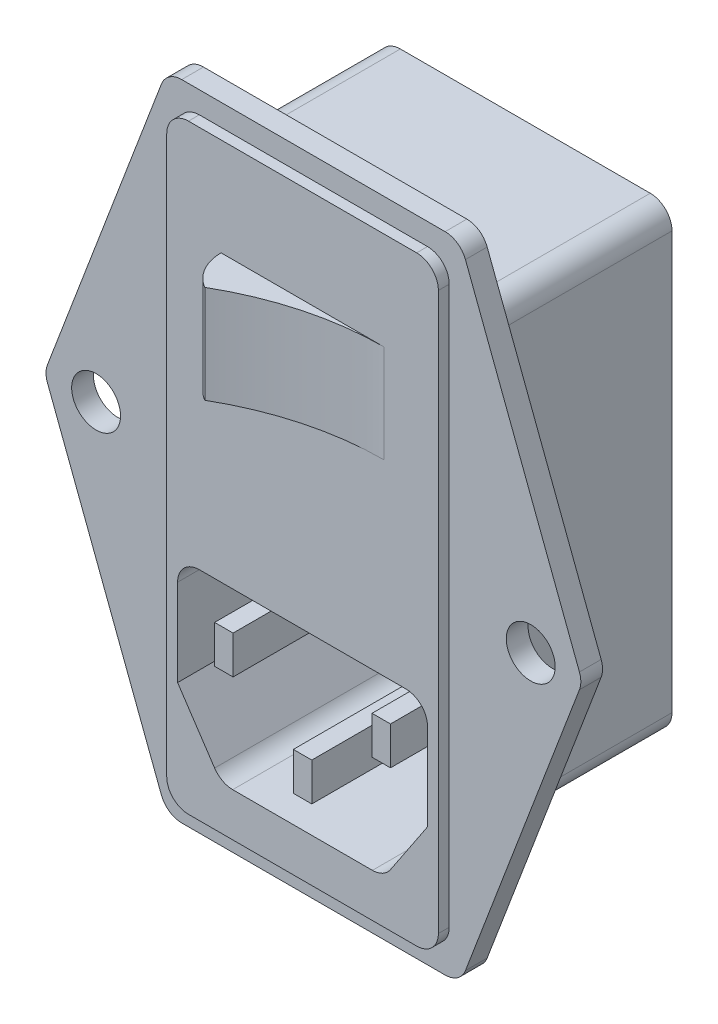
SolidWorks part; units mm, degrees
ref_plane "Спереди" through (0, 0, 0) normal (0, 0, 1) x (1, 0, 0)
ref_plane "Сверху" through (0, 0, 0) normal (0, 1, 0) x (1, 0, 0)
ref_plane "Справа" through (0, 0, 0) normal (1, 0, 0) x (0, 0, -1)
sketch "Эскиз1" plane through (0, 0, 0) normal (0, 0, 1) x (1, 0, 0)
  line L0 (0, 0) -> (27, 0)
  line L1 (0, 0) -> (0, -41.25)
  line L2 (27, 0) -> (27, -41.25)
  line L3 (0, -41.25) -> (27, -41.25) construction
  line L4 (13.5, 0) -> (13.5, -41.25) construction
  line L5 (13.5, -41.25) -> (13.5, -47.25) construction
  line L6 (6.25, -47.25) -> (20.75, -47.25)
  line L7 (0, -41.25) -> (6.25, -47.25)
  line L8 (20.75, -47.25) -> (27, -41.25)
  dimension "D1" = 27
  dimension "D2" = 41.25
  dimension "D3" = 47.25
  dimension "D4" = 14.5
extrude "Бобышка-Вытянуть1" add sketch "Эскиз1" along normal blind 17.5
sketch "Эскиз2" plane through (0, 0, 17.5) normal (0, 0, 1) x (1, 0, 0)
  line L0 (13.5, 0) -> (13.5, -47.25) construction
  line L1 (27, 0) -> (0, 0) construction
  line L2 (6.25, -47.25) -> (20.75, -47.25) construction
  line L3 (13.5, 0) -> (13.5, 7) construction
  line L4 (13.5, -47.25) -> (13.5, -52.25) construction
  line L5 (0, 7) -> (27, 7)
  line L6 (0, -52.25) -> (27, -52.25)
  line L7 (27, 7) -> (27, -52.25) construction
  line L8 (27, -22.625) -> (13.5, -22.625) construction
  line L9 (38.25, -22.625) -> (-11.25, -22.625) construction
  line L10 (0, 7) -> (-11.25, -22.625)
  line L11 (-11.25, -22.625) -> (0, -52.25)
  line L12 (27, 7) -> (38.25, -22.625)
  line L13 (38.25, -22.625) -> (27, -52.25)
  dimension "D1" = 5
  dimension "D2" = 7
  dimension "D3" = 27
  dimension "D4" = 49.5
extrude "Бобышка-Вытянуть2" add sketch "Эскиз2" along normal blind 2
sketch "Эскиз3" plane through (0, 0, 19.5) normal (0, 0, 1) x (1, 0, 0)
  line L0 (13.5, 7) -> (13.5, -52.25) construction
  line L1 (27, 7) -> (0, 7) construction
  line L2 (0, -52.25) -> (27, -52.25) construction
  line L3 (1, 5) -> (26, 5)
  line L4 (1, 5) -> (1, -50.25)
  line L5 (26, 5) -> (26, -50.25)
  line L6 (1, -50.25) -> (26, -50.25)
  line L7 (26, -22.625) -> (1, -22.625) construction
  point P10 (13.5, -22.625)
  dimension "D1" = 2
  dimension "D2" = 25
extrude "Бобышка-Вытянуть3" add sketch "Эскиз3" along normal blind 1
fillet "Скругление1" radius 2 4 edges at (0, 7, 18.5) (27, -52.25, 18.5) (38.25, -22.625, 18.5) (27, 7, 18.5)
fillet "Скругление2" radius 2 2 edges at (0, -52.25, 18.5) (-11.25, -22.625, 18.5)
fillet "Скругление3" radius 2 4 edges at (26, 5, 20) (26, -50.25, 20) (1, -50.25, 20) (1, 5, 20)
sketch "Эскиз4" plane through (0, 0, 20.5) normal (0, 0, 1) x (1, 0, 0)
  line L0 (13.5, 5) -> (13.5, -50.25) construction
  line L1 (24, 5) -> (3, 5) construction
  line L2 (3, -50.25) -> (24, -50.25) construction
  line L3 (6, -4) -> (21, -4)
  line L4 (6, -4) -> (6, -13)
  line L5 (21, -4) -> (21, -13)
  line L6 (6, -13) -> (21, -13)
  line L7 (13.5, -4) -> (13.5, -13) construction
  dimension "D1" = 9
  dimension "D2" = 15
  dimension "D3" = 9
extrude "Бобышка-Вытянуть4" add sketch "Эскиз4" along normal blind 3.5
sketch "Эскиз5" plane through (0, -4, 0) normal (0, 1, 0) x (1, 0, 0)
  line L0 (21, -24) -> (6, -24) construction
  line L1 (6, -24) -> (6, -20.5) construction
  line L2 (6, -24) -> (6, -20.5)
  line L3 (21, -24) -> (6, -24)
  line L4 (21, -20.5) -> (6, -20.5) construction
  line L5 (21, -24) -> (21, -20.5) construction
  line L6 (21, -24) -> (21, -20.5)
  arc A0 (21, -20.5) -> (8, -24) centre (21, -46.3929) ccw
  arc A1 (6, -20.5) -> (8, -24) centre (10.0625, -20.5) ccw
  point P2 (8, -24)
  line M3 (6, -20.5) -> (6, -24)
  line M4 (6, -24) -> (21, -24)
  line M5 (21, -24) -> (21, -20.5)
  dimension "D1" = 2
extrude "Вырез-Вытянуть1" cut sketch "Эскиз5" against normal up to surface (9 mm away) contours A0 L3 M5 | A1 M3 M4 region at (16.0778, -4, 22.5916) region at (6.5621, -4, 23.1738) up to face at (13.5, -13, 22.25)
sketch "Эскиз6" plane through (0, 0, 20.5) normal (0, 0, 1) x (1, 0, 0)
  line L0 (4, -30.25) -> (23, -30.25)
  line L1 (2, -30.25) -> (2, -46.25) construction
  line L2 (25, -30.25) -> (25, -46.25) construction
  line L3 (2, -46.25) -> (25, -46.25) construction
  line L4 (3, -50.25) -> (24, -50.25) construction
  line L5 (13.5, 5) -> (13.5, -50.25) construction
  line L6 (24, 5) -> (3, 5) construction
  line L7 (2, -40.25) -> (5.4063, -45.3594)
  line L8 (7.0704, -46.25) -> (19.9296, -46.25)
  line L9 (2, -32.25) -> (2, -40.25)
  line L10 (2, -40.25) -> (25, -40.25) construction
  line L11 (21.5937, -45.3594) -> (25, -40.25)
  line L12 (25, -40.25) -> (25, -32.25)
  line L13 (5.4063, -33.75) -> (5.4063, -37.25)
  line L14 (5.4063, -33.75) -> (7.1063, -33.75)
  line L15 (5.4063, -37.25) -> (7.1063, -37.25)
  line L16 (7.1063, -33.75) -> (7.1063, -37.25)
  line L17 (19.8937, -33.75) -> (21.5937, -33.75)
  line L18 (19.8937, -33.75) -> (19.8937, -37.25)
  line L19 (21.5937, -33.75) -> (21.5937, -37.25)
  line L20 (19.8937, -37.25) -> (21.5937, -37.25)
  line L21 (12.65, -40.25) -> (14.35, -40.25)
  line L22 (12.65, -40.25) -> (12.65, -43.75)
  line L23 (14.35, -40.25) -> (14.35, -43.75)
  line L24 (12.65, -43.75) -> (14.35, -43.75)
  line L25 (7.1063, -37.25) -> (19.8937, -37.25) construction
  arc A0 (7.0704, -46.25) -> (5.4063, -45.3594) centre (7.0704, -44.25) cw
  arc A1 (19.9296, -46.25) -> (21.5937, -45.3594) centre (19.9296, -44.25) ccw
  arc A2 (25, -32.25) -> (23, -30.25) centre (23, -32.25) ccw
  arc A3 (4, -30.25) -> (2, -32.25) centre (4, -32.25) ccw
  point P8 (13.5, -30.25)
  point P13 (13.5, -46.25)
  point P18 (6, -46.25)
  point P21 (21, -46.25)
  point P28 (13.5, -37.25)
  point P35 (13.5, -40.25)
  dimension "D6" = 2
  dimension "D1" = 4
  dimension "D2" = 23
  dimension "D3" = 16
  dimension "D4" = 15
  dimension "D5" = 10
  dimension "D7" = 1.7
  dimension "D8" = 3.5
  dimension "D9" = 3
extrude "Вырез-Вытянуть2" cut sketch "Эскиз6" against normal blind 18
fillet "Скругление4" radius 2 6 edges at (6.25, -47.25, 8.75) (0, -41.25, 8.75) (0, 0, 8.75) (20.75, -47.25, 8.75) (27, -41.25, 8.75) (27, 0, 8.75)
sketch "Эскиз7" plane through (0, 0, 0) normal (0, 0, -1) x (-1, 0, 0)
  line L0 (-23.5, -1.5) -> (-3.5, -1.5)
  line L1 (-25.5, -3.5) -> (-25.5, -14.5)
  line L2 (-1.5, -3.5) -> (-1.5, -14.5)
  line L3 (-23.5, -16.5) -> (-3.5, -16.5)
  line L4 (-27, -40.3976) -> (-27, -2) construction
  line L5 (-25, 0) -> (-2, 0) construction
  line L6 (0, -2) -> (0, -40.3976) construction
  arc A0 (-23.5, -16.5) -> (-25.5, -14.5) centre (-23.5, -14.5) cw
  arc A1 (-3.5, -16.5) -> (-1.5, -14.5) centre (-3.5, -14.5) ccw
  arc A2 (-1.5, -3.5) -> (-3.5, -1.5) centre (-3.5, -3.5) ccw
  arc A3 (-25.5, -3.5) -> (-23.5, -1.5) centre (-23.5, -3.5) cw
  point P14 (-1.5, -16.5)
  point P17 (-1.5, -1.5)
  dimension "D5" = 2
  dimension "D1" = 1.5
  dimension "D2" = 1.5
  dimension "D3" = 1.5
  dimension "D4" = 15
extrude "Вырез-Вытянуть3" cut sketch "Эскиз7" against normal blind 7
sketch "Эскиз8" plane through (0, 0, 0) normal (0, 0, -1) x (-1, 0, 0)
  line L0 (-7, -19.5) -> (-2, -19.5)
  line L1 (-7, -19.5) -> (-7, -20.5)
  line L2 (-2, -19.5) -> (-2, -20.5)
  line L3 (-7, -20.5) -> (-2, -20.5)
  line L4 (-7, -32.5) -> (-2, -32.5)
  line L5 (-7, -32.5) -> (-7, -33.5)
  line L6 (-2, -32.5) -> (-2, -33.5)
  line L7 (-7, -33.5) -> (-2, -33.5)
  line L8 (-16, -43.25) -> (-11, -43.25)
  line L9 (-16, -43.25) -> (-16, -44.25)
  line L10 (-11, -43.25) -> (-11, -44.25)
  line L11 (-16, -44.25) -> (-11, -44.25)
  line L12 (0, -2) -> (0, -40.3976) construction
  line L13 (-13.5, -16.5) -> (-13.5, -47.25) construction
  line L14 (-23.5, -16.5) -> (-3.5, -16.5) construction
  line L15 (-7.0546, -47.25) -> (-19.9454, -47.25) construction
  point P20 (-13.5, -43.25)
  dimension "D1" = 1
  dimension "D2" = 5
  dimension "D3" = 2
  dimension "D4" = 12
  dimension "D5" = 3
  dimension "D6" = 3
extrude "Бобышка-Вытянуть5" add sketch "Эскиз8" along normal blind 9.5
sketch "Эскиз9" plane through (0, 0, 7) normal (0, 0, -1) x (-1, 0, 0)
  line L0 (-7.5, -6.5) -> (-6.5, -6.5)
  line L1 (-7.5, -6.5) -> (-7.5, -11.5)
  line L2 (-6.5, -6.5) -> (-6.5, -11.5)
  line L3 (-7.5, -11.5) -> (-6.5, -11.5)
  line L4 (-14.5, -6.5) -> (-13.5, -6.5)
  line L5 (-14.5, -6.5) -> (-14.5, -11.5)
  line L6 (-13.5, -6.5) -> (-13.5, -11.5)
  line L7 (-14.5, -11.5) -> (-13.5, -11.5)
  line L8 (-1.5, -14.5) -> (-1.5, -3.5) construction
  line L9 (-1.5, -9) -> (-25.5, -9) construction
  line L10 (-1.5, -14.5) -> (-1.5, -3.5) construction
  line L14 (-25.5, -3.5) -> (-25.5, -14.5) construction
  point P17 (-6.5, -9)
  dimension "D1" = 1
  dimension "D2" = 5
  dimension "D3" = 7
  dimension "D4" = 5
extrude "Бобышка-Вытянуть6" add sketch "Эскиз9" along normal up to surface (7 mm away) up to face at (4.5, -33, 0)
sketch "Эскиз10" plane through (0, 0, 19.5) normal (0, 0, 1) x (1, 0, 0)
  line L0 (-6.5, -22.625) -> (33.5, -22.625) construction
  line L1 (26, -48.25) -> (26, 3) construction
  line L2 (1, 3) -> (1, -48.25) construction
  line L3 (26, -48.25) -> (26, 3) construction
  line L4 (1, 3) -> (1, -48.25) construction
  line L5 (13.5, 7) -> (13.5, -52.25) construction
  line L8 (25.6201, 7) -> (1.3799, 7) construction
  line L9 (1.3799, -52.25) -> (25.6201, -52.25) construction
  circle A0 centre (-6.5, -22.625) radius 2.25
  circle A1 centre (33.5, -22.625) radius 2.25
  point P6 (26, -22.625)
  point P14 (13.5, -22.625)
  dimension "D2" = 4.5
  dimension "D1" = 40
extrude "Вырез-Вытянуть4" cut sketch "Эскиз10" against normal through all
sketch "Эскиз11" plane through (0, 0, 20.5) normal (0, 0, 1) x (1, 0, 0)
  line L0 (13.5, 5) -> (13.5, -50.25) construction
  line L1 (24, 5) -> (3, 5) construction
  line L2 (3, -50.25) -> (24, -50.25) construction
  line L3 (-6.5, -22.625) -> (33.5, -22.625) construction
ref_plane "x" through (13.5, 0, 0) normal (-1, 0, 0) x (0, -1, 0)
ref_plane "y" through (0, -22.625, 0) normal (0, -1, 0) x (1, 0, 0)
